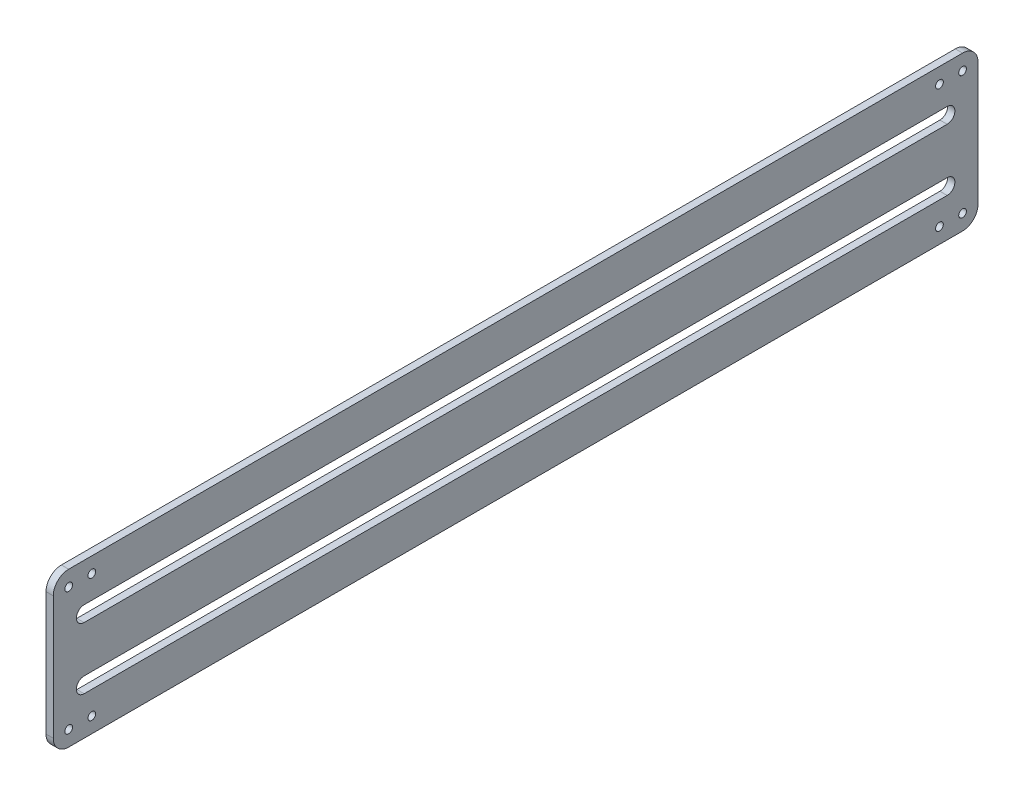
SolidWorks part; units mm, degrees
ref_plane "Front Plane" through (0, 0, 0) normal (0, 0, 1) x (1, 0, 0)
ref_plane "Top Plane" through (0, 0, 0) normal (0, 1, 0) x (1, 0, 0)
ref_plane "Right Plane" through (0, 0, 0) normal (1, 0, 0) x (0, 0, -1)
sketch "Sketch1" plane through (0, 0, 0) normal (1, 0, 0) x (0, 0, -1)
  line L1 (-184.15, -31.75) -> (184.15, -31.75)
  line L2 (-190.5, -25.4) -> (-190.5, 25.4)
  line L3 (-184.15, 31.75) -> (184.15, 31.75)
  line L4 (190.5, -25.4) -> (190.5, 25.4)
  line L5 (-190.5, -31.75) -> (190.5, 31.75) construction
  line L6 (-190.5, 31.75) -> (190.5, -31.75) construction
  arc A0 (184.15, 31.75) -> (190.5, 25.4) centre (184.15, 25.4) cw
  arc A1 (190.5, -25.4) -> (184.15, -31.75) centre (184.15, -25.4) cw
  arc A2 (-184.15, -31.75) -> (-190.5, -25.4) centre (-184.15, -25.4) cw
  arc A3 (-190.5, 25.4) -> (-184.15, 31.75) centre (-184.15, 25.4) cw
  point P0 (0, 0)
  dimension "D3" = 6.35
  dimension "D1" = 381
  dimension "D2" = 63.5
extrude "Outer Cut" add sketch "Sketch1" along normal mid plane 2.9972
sketch "Sketch2" plane through (1.4986, 0, 0) normal (1, 0, 0) x (0, 0, -1)
  line L0 (-190.5, 0) -> (190.5, 0) construction
  line L1 (-190.5, 25.4) -> (-190.5, -25.4) construction
  line L2 (190.5, -25.4) -> (190.5, 25.4) construction
  line L3 (-177.8, 12.7) -> (177.8, 12.7) construction
  line L4 (-177.8, 15.875) -> (177.8, 15.875)
  line L5 (-177.8, 9.525) -> (177.8, 9.525)
  line L6 (-177.8, -12.7) -> (177.8, -12.7) construction
  line L7 (-177.8, -15.875) -> (177.8, -15.875)
  line L8 (-177.8, -9.525) -> (177.8, -9.525)
  arc A0 (-177.8, 15.875) -> (-177.8, 9.525) centre (-177.8, 12.7) ccw
  arc A1 (177.8, 9.525) -> (177.8, 15.875) centre (177.8, 12.7) ccw
  arc A2 (-177.8, -15.875) -> (-177.8, -9.525) centre (-177.8, -12.7) cw
  arc A3 (177.8, -9.525) -> (177.8, -15.875) centre (177.8, -12.7) cw
  point P2 (0, 12.7)
  point P16 (0, -12.7)
  dimension "D1" = 6.35
  dimension "D2" = 25.4
  dimension "D3" = 12.7
  dimension "D4" = 12.7
extrude "Slots" cut sketch "Sketch2" against normal through all
sketch "Sketch3" plane through (1.4986, 0, 0) normal (1, 0, 0) x (0, 0, -1)
  line L0 (-190.5, 25.4) -> (-190.5, -25.4) construction
  line L1 (184.15, 31.75) -> (-184.15, 31.75) construction
  line L2 (0, 0) -> (0, 31.75) construction
  line L3 (0, 0) -> (-190.5, 0) construction
  circle A0 centre (-184.15, 25.4) radius 1.5875
  circle A1 centre (-174.625, 25.4) radius 1.5875
  circle A2 centre (-174.625, -25.4) radius 1.5875
  circle A3 centre (-184.15, -25.4) radius 1.5875
  circle A4 centre (174.625, 25.4) radius 1.5875
  circle A5 centre (184.15, 25.4) radius 1.5875
  circle A6 centre (184.15, -25.4) radius 1.5875
  circle A7 centre (174.625, -25.4) radius 1.5875
  dimension "D1" = 3.175
  dimension "D2" = 6.35
  dimension "D3" = 6.35
  dimension "D5" = 9.525
  dimension "D4" = 2
extrude "Mount Holes" cut sketch "Sketch3" against normal through all
